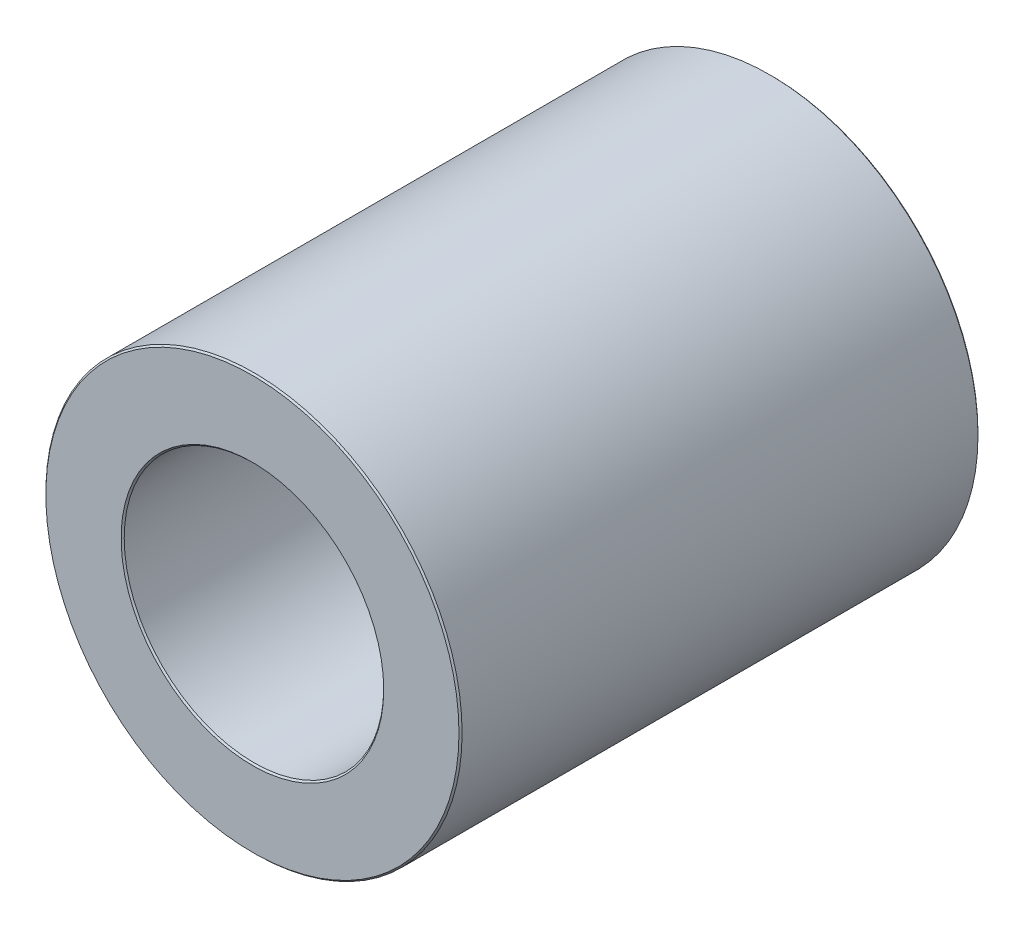
SolidWorks part; units mm, degrees
material "Brass"
ref_plane "Front Plane" through (0, 0, 0) normal (0, 0, 1) x (1, 0, 0)
ref_plane "Top Plane" through (0, 0, 0) normal (0, 1, 0) x (1, 0, 0)
ref_plane "Right Plane" through (0, 0, 0) normal (1, 0, 0) x (0, 0, -1)
sketch "Sketch1" plane through (0, 0, 0) normal (0, 0, 1) x (1, 0, 0)
  circle A0 centre (0, 0) radius 4.01
  circle A1 centre (0, 0) radius 2.5
  point P8 (0, -4.01)
  point P9 (0, 4.01)
  dimension "ID" = 5
  dimension "OD" = 8.02
sketch "Sketch2" plane through (0, 0, 0) normal (1, 0, 0) x (0, 0, -1)
  line L0 (5, 0) -> (-5, 0) construction
  line L1 (5, 4.01) -> (-5, 4.01) construction
  point P4 (0, 0)
  point P8 (0, 4.01)
  point P9 (0, 4.01)
  dimension "Length" = 10
sketch "Sketch5" plane through (0, 0, 0) normal (0, 0, 1) x (1, 0, 0)
  circle A0 centre (0, 0) radius 2.5 construction
  circle A1 centre (0, 0) radius 4.01 construction
  circle A2 centre (0, 0) radius 2.5
  circle A3 centre (0, 0) radius 4.01
extrude "Boss-Extrude1" add sketch "Sketch5" along normal up to vertex and the other way up to vertex up to point (0, 0, 5) other way up to point (0, 0, -5)
chamfer "Chamfer1" distance 0.03 angle 45 4 edges at (4.01, 0, -5) (2.5, 0, -5) (2.5, 0, 5) (4.01, 0, 5)
equation "\"D1@Chamfer1\"=\"ID@Sketch1\"*.006"
